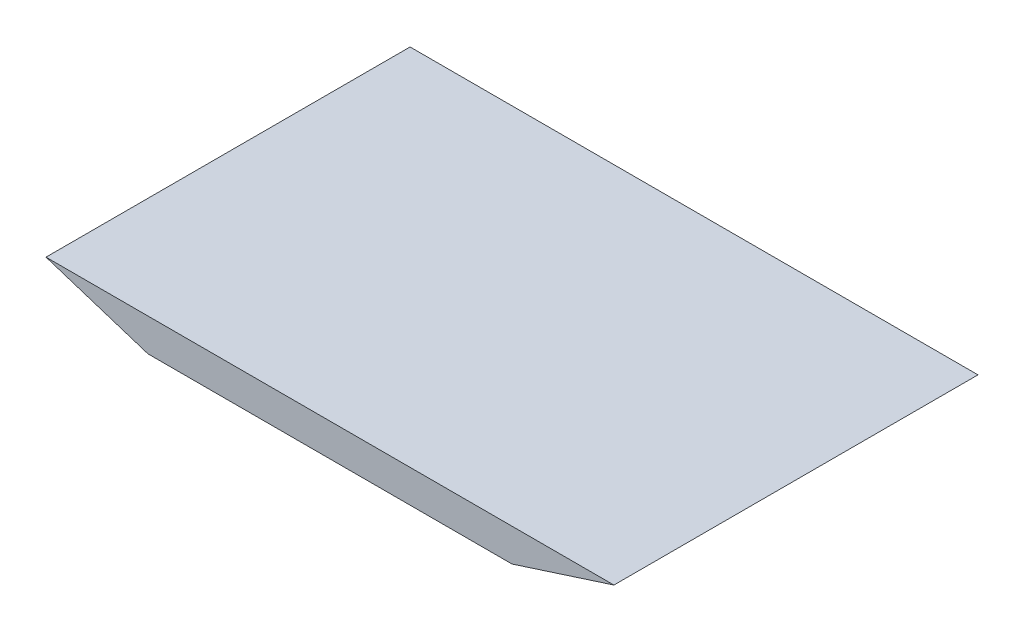
SolidWorks part; units mm, degrees
ref_plane "Front Plane" through (0, 0, 0) normal (0, 0, 1) x (1, 0, 0)
ref_plane "Top Plane" through (0, 0, 0) normal (0, 1, 0) x (1, 0, 0)
ref_plane "Right Plane" through (0, 0, 0) normal (1, 0, 0) x (0, 0, -1)
sketch "Sketch1" plane through (0, 0, 0) normal (0, 0, 1) x (1, 0, 0)
  line L0 (0, 0) -> (156, 0)
  line L1 (156, 0) -> (128, -9)
  line L2 (128, -9) -> (28, -9)
  line L3 (28, -9) -> (0, 0)
  dimension "D1" = 100
  dimension "D2" = 9
  dimension "D3" = 28
  dimension "D4" = 28
extrude "Boss-Extrude1" add sketch "Sketch1" along normal blind 100
